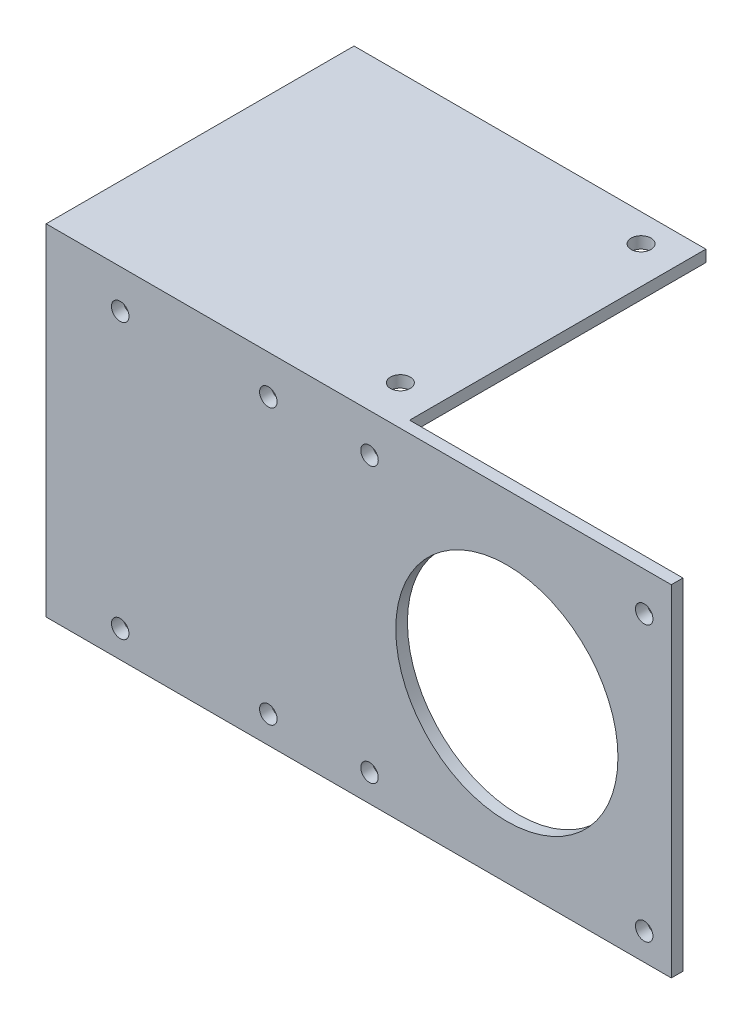
SolidWorks part; units mm, degrees
ref_plane "Front Plane" through (0, 0, 0) normal (0, 0, 1) x (1, 0, 0)
ref_plane "Top Plane" through (0, 0, 0) normal (0, 1, 0) x (1, 0, 0)
ref_plane "Right Plane" through (0, 0, 0) normal (1, 0, 0) x (0, 0, -1)
sketch "Sketch1" plane through (0, 0, 0) normal (0, 0, 1) x (1, 0, 0)
  line L0 (102.55, 51.75) -> (12.7, 51.75) construction
  line L1 (0, 58.4) -> (107.2, 58.4)
  line L2 (0, 58.4) -> (0, 0)
  line L3 (0, 0) -> (107.2, 0)
  line L4 (107.2, 58.4) -> (107.2, 0)
  line L5 (102.55, 51.75) -> (102.55, 4.65) construction
  line L6 (12.7, 51.75) -> (12.7, 4.65) construction
  line L7 (55.45, 4.65) -> (55.45, 51.75) construction
  line L8 (12.7, 4.65) -> (102.55, 4.65) construction
  line L9 (38.1, 51.75) -> (38.1, 4.65) construction
  line L10 (55.45, 51.75) -> (102.55, 4.65) construction
  line L11 (102.55, 51.75) -> (55.45, 4.65) construction
  circle A0 centre (102.55, 51.75) radius 1.5
  circle A1 centre (102.55, 4.65) radius 1.5
  circle A2 centre (55.45, 4.65) radius 1.5
  circle A3 centre (55.45, 51.75) radius 1.5
  circle A4 centre (12.7, 51.75) radius 1.5
  circle A5 centre (38.1, 51.75) radius 1.5
  circle A6 centre (12.7, 4.65) radius 1.5
  circle A7 centre (38.1, 4.65) radius 1.5
  circle A8 centre (79, 28.2) radius 19.05
  point P21 (0, 0)
  dimension "D3" = 3
  dimension "D10" = 38.1
  dimension "D1" = 58.4
  dimension "D2" = 107.2
  dimension "D4" = 47.1
  dimension "D5" = 47.1
  dimension "D6" = 4.65
  dimension "D7" = 25.4
  dimension "D8" = 4.65
  dimension "D9" = 12.7
extrude "Boss-Extrude1" add sketch "Sketch1" against normal blind 2
sketch "Sketch2" plane through (0, 0, -2) normal (0, 0, -1) x (-1, 0, 0)
  line L0 (0, 58.4) -> (0, 56.4)
  line L1 (0, 58.4) -> (0, 0) construction
  line L2 (0, 56.4) -> (-60.325, 56.4)
  line L3 (-60.325, 56.4) -> (-60.325, 58.4)
  line L4 (-107.2, 58.4) -> (0, 58.4) construction
  line L5 (-60.325, 58.4) -> (0, 58.4)
  dimension "D1" = 60.325
  dimension "D2" = 2
extrude "Boss-Extrude2" add sketch "Sketch2" along normal blind 50.8
sketch "Sketch3" plane through (0, 58.4, 0) normal (0, 1, 0) x (1, 0, 0)
  line L0 (53.975, 48.0375) -> (53.975, 6.7625) construction
  line L1 (0, 52.8) -> (60.325, 52.8) construction
  line L2 (60.325, 52.8) -> (60.325, 2) construction
  circle A0 centre (53.975, 48.0375) radius 1.7
  circle A1 centre (53.975, 6.7625) radius 1.7
  point P4 (48.3006, 48.3384)
  point P7 (0, 0)
  dimension "D1" = 3.4
  dimension "D2" = 41.275
  dimension "D3" = 4.7625
  dimension "D4" = 6.35
extrude "Cut-Extrude1" cut sketch "Sketch3" against normal through all
